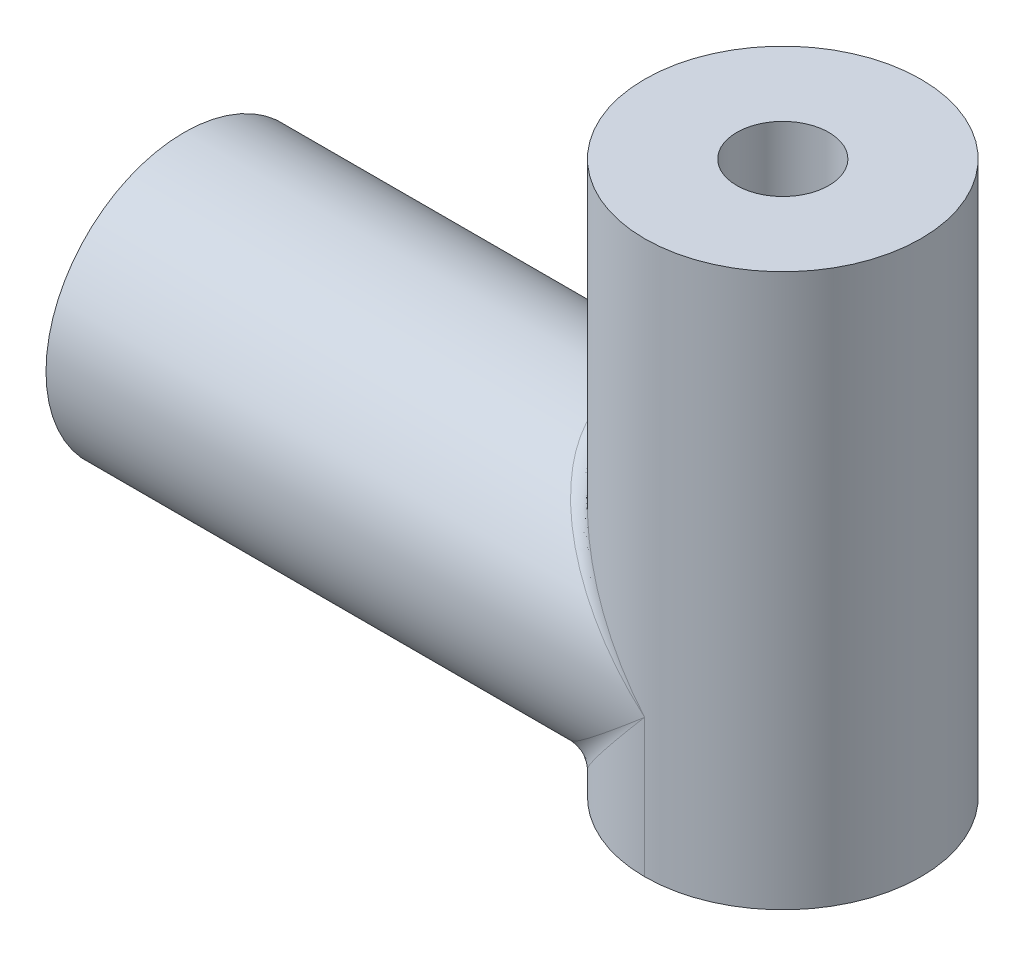
SolidWorks part; units mm, degrees
ref_plane "Front Plane" through (0, 0, 0) normal (0, 0, 1) x (1, 0, 0)
ref_plane "Top Plane" through (0, 0, 0) normal (0, 1, 0) x (1, 0, 0)
ref_plane "Right Plane" through (0, 0, 0) normal (1, 0, 0) x (0, 0, -1)
sketch "Sketch3" plane through (0, 0, 0) normal (0, 1, 0) x (1, 0, 0)
  circle A0 centre (0, 0) radius 1
  circle A1 centre (0, 0) radius 3
  dimension "D1" = 2
  dimension "D2" = 6
extrude "Boss-Extrude1" add sketch "Sketch3" along normal blind 12
ref_plane "Plane1" through (-3, 0, 0) normal (-1, 0, 0) x (0, 0, 1)
sketch "Sketch4" plane through (-3, 0, 0) normal (-1, 0, 0) x (0, 0, 1)
  line L0 (0, 12) -> (0, 0) construction
  line L1 (1, 12) -> (-1, 12) construction
  line L2 (-3, 0) -> (3, 0) construction
  circle A0 centre (0, 3) radius 3
  point P6 (0, 3)
  dimension "D1" = 6
extrude "Boss-Extrude2" add sketch "Sketch4" along normal blind 10 and the other way up to surface
sketch "Sketch5" plane through (-13, 0, 0) normal (-1, 0, 0) x (0, 0, 1)
  circle A0 centre (0, 3) radius 1.6
  point P0 (0, 3)
  dimension "D1" = 3.2
extrude "Cut-Extrude1" cut sketch "Sketch5" against normal blind 10
fillet "Fillet1" radius 0.5 3 edges at (-2.1213, 0.8787, 2.1213) (-2.1213, 0.8787, -2.1213) (-3, 6, 0)
